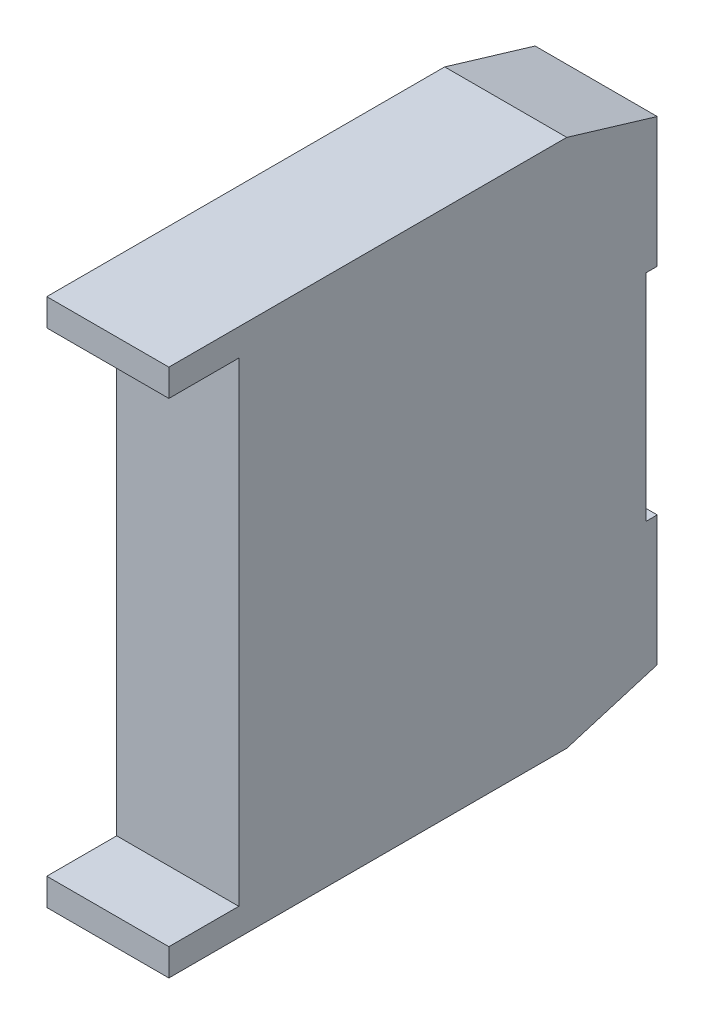
SolidWorks part; units mm, degrees
ref_plane "前视基准面" through (0, 0, 0) normal (0, 0, 1) x (1, 0, 0)
ref_plane "上视基准面" through (0, 0, 0) normal (0, 1, 0) x (1, 0, 0)
ref_plane "右视基准面" through (0, 0, 0) normal (1, 0, 0) x (0, 0, -1)
sketch "草图1" plane through (0, 0, 0) normal (1, 0, 0) x (0, 0, -1)
  line L0 (0, 52.9257) -> (0, -65.8977) construction
  line L1 (-128.0336, 0) -> (98.198, 0) construction
  line L2 (0, 17.5) -> (0, 19.5)
  line L3 (5.1533, 17.5) -> (5.1533, -17.5)
  line L4 (0, 19.5) -> (29.333, 19.5)
  line L5 (29.333, 19.5) -> (36, 17.5)
  line L6 (36, 17.5) -> (36, 7.9341)
  line L7 (0, 17.5) -> (5.1533, 17.5)
  line L8 (36, 7.9341) -> (35.1809, 7.9341)
  line L9 (35.1809, 7.9341) -> (35.1809, -7.9341)
  line L10 (36, -7.9341) -> (35.1809, -7.9341)
  line L11 (0, -17.5) -> (5.1533, -17.5)
  line L12 (36, -17.5) -> (36, -7.9341)
  line L13 (29.333, -19.5) -> (36, -17.5)
  line L14 (0, -19.5) -> (29.333, -19.5)
  line L15 (0, -17.5) -> (0, -19.5)
  point P14 (5.1533, 0)
  point P16 (35.1809, 0)
  point P22 (5.1533, 0)
  dimension "D1" = 36
  dimension "D2" = 39
extrude "凸台-拉伸1" add sketch "草图1" along normal blind 4.5 and the other way blind 4.5
